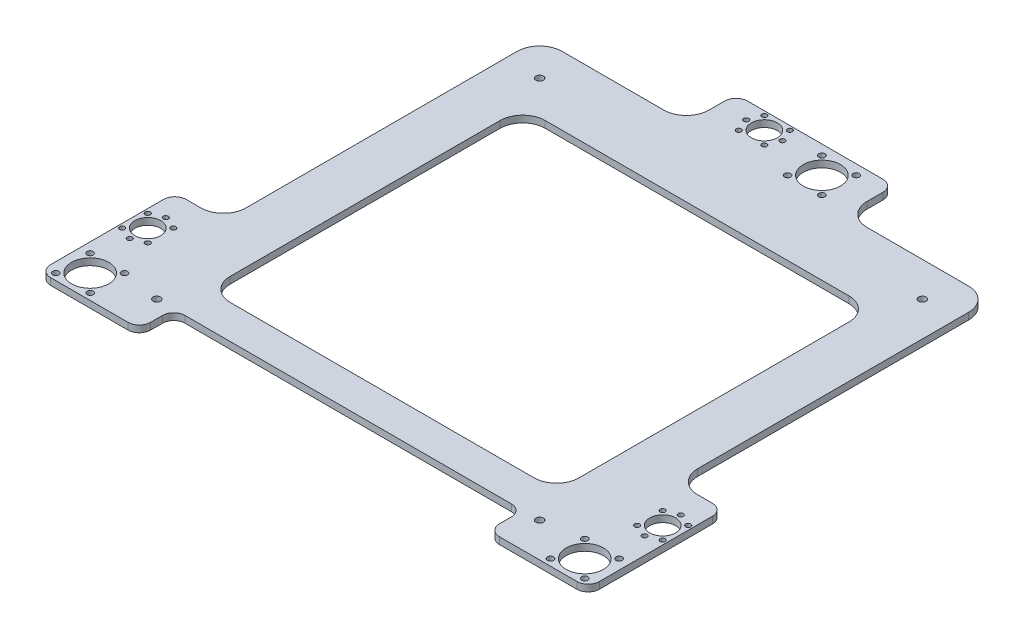
SolidWorks part; units mm, degrees
material "Plain Carbon Steel"
ref_plane "Front Plane" through (0, 0, 0) normal (0, 0, 1) x (1, 0, 0)
ref_plane "Top Plane" through (0, 0, 0) normal (0, 1, 0) x (1, 0, 0)
ref_plane "Right Plane" through (0, 0, 0) normal (1, 0, 0) x (0, 0, -1)
sketch "Sketch1" plane through (0, 0, 0) normal (0, 1, 0) x (1, 0, 0)
  line L0 (-243, -200) -> (243, -200)
  line L1 (-169.5, 169.5) -> (169.5, 169.5)
  line L2 (-169.5, 169.5) -> (-169.5, -169.5)
  line L3 (-169.5, -169.5) -> (169.5, -169.5)
  line L4 (169.5, 169.5) -> (169.5, -169.5)
  line L5 (-169.5, 169.5) -> (169.5, -169.5) construction
  line L6 (-169.5, -169.5) -> (169.5, 169.5) construction
  line L7 (-243, -200) -> (-243, 244)
  line L8 (-243, 244) -> (243, 244)
  line L9 (243, 244) -> (243, -200)
  line L10 (0, 0) -> (0, -200)
  point P0 (0, 0)
  point P12 (0, 0)
  point P13 (0, 0)
  point P14 (0, 0)
  point P15 (0, 0)
  dimension "D1" = 339
  dimension "D2" = 444
  dimension "D3" = 486
  dimension "D4" = 200
sketch "Sketch2" plane through (0, 0, 0) normal (0, 1, 0) x (1, 0, 0)
  line L0 (243, 244) -> (243, -200) construction
  line L1 (-243, 244) -> (243, 244) construction
  line L2 (-243, -200) -> (-243, 244) construction
  line L3 (-243, -200) -> (243, -200) construction
  line L4 (243, 244) -> (243, -200)
  line L5 (-243, 244) -> (243, 244)
  line L6 (-243, -200) -> (-243, 244)
  line L7 (-243, -200) -> (243, -200)
extrude "Boss-Extrude1" add sketch "Sketch2" along normal blind 6
sketch "Sketch3" plane through (0, 6, 0) normal (0, 1, 0) x (1, 0, 0)
  circle A0 centre (-234.2028, -194.2028) radius 2.75 construction
  circle A1 centre (-203.7972, -194.2028) radius 2.75 construction
  circle A2 centre (-203.7972, -163.7972) radius 2.75 construction
  circle A3 centre (-234.2028, -163.7972) radius 2.75 construction
  circle A4 centre (-234.2028, -194.2028) radius 2.75
  circle A5 centre (-203.7972, -194.2028) radius 2.75
  circle A6 centre (-203.7972, -163.7972) radius 2.75
  circle A7 centre (-234.2028, -163.7972) radius 2.75
  circle A8 centre (-239.3137, -130.3137) radius 2.35 construction
  circle A9 centre (-239.3137, -130.3137) radius 2.35 construction
  circle A10 centre (-239.3137, -107.6863) radius 2.35 construction
  circle A11 centre (-239.3137, -107.6863) radius 2.35 construction
  circle A12 centre (-228, -103) radius 2.35 construction
  circle A13 centre (-228, -103) radius 2.35 construction
  circle A14 centre (-216.6863, -107.6863) radius 2.35 construction
  circle A15 centre (-216.6863, -107.6863) radius 2.35 construction
  circle A16 centre (-216.6863, -130.3137) radius 2.35 construction
  circle A17 centre (-216.6863, -130.3137) radius 2.35 construction
  circle A18 centre (-228, -135) radius 2.35 construction
  circle A19 centre (-228, -135) radius 2.35 construction
  circle A20 centre (-239.3137, -130.3137) radius 2.35
  circle A21 centre (-239.3137, -130.3137) radius 2.35
  circle A22 centre (-239.3137, -107.6863) radius 2.35
  circle A23 centre (-239.3137, -107.6863) radius 2.35
  circle A24 centre (-228, -103) radius 2.35
  circle A25 centre (-228, -103) radius 2.35
  circle A26 centre (-216.6863, -107.6863) radius 2.35
  circle A27 centre (-216.6863, -107.6863) radius 2.35
  circle A28 centre (-216.6863, -130.3137) radius 2.35
  circle A29 centre (-216.6863, -130.3137) radius 2.35
  circle A30 centre (-228, -135) radius 2.35
  circle A31 centre (-228, -135) radius 2.35
  circle A32 centre (-228, -119) radius 11 construction
  circle A33 centre (-219, -179) radius 16 construction
  circle A34 centre (-228, -119) radius 11
  circle A35 centre (-219, -179) radius 16
  circle A36 centre (-41.3137, 240.3137) radius 2.35 construction
  circle A37 centre (-41.3137, 240.3137) radius 2.35 construction
  circle A38 centre (-18.6863, 240.3137) radius 2.35 construction
  circle A39 centre (-18.6863, 240.3137) radius 2.35 construction
  circle A40 centre (-14, 229) radius 2.35 construction
  circle A41 centre (-14, 229) radius 2.35 construction
  circle A42 centre (-18.6863, 217.6863) radius 2.35 construction
  circle A43 centre (-18.6863, 217.6863) radius 2.35 construction
  circle A44 centre (-41.3137, 217.6863) radius 2.35 construction
  circle A45 centre (-41.3137, 217.6863) radius 2.35 construction
  circle A46 centre (-46, 229) radius 2.35 construction
  circle A47 centre (-46, 229) radius 2.35 construction
  circle A48 centre (-41.3137, 240.3137) radius 2.35
  circle A49 centre (-41.3137, 240.3137) radius 2.35
  circle A50 centre (-18.6863, 240.3137) radius 2.35
  circle A51 centre (-18.6863, 240.3137) radius 2.35
  circle A52 centre (-14, 229) radius 2.35
  circle A53 centre (-14, 229) radius 2.35
  circle A54 centre (-18.6863, 217.6863) radius 2.35
  circle A55 centre (-18.6863, 217.6863) radius 2.35
  circle A56 centre (-41.3137, 217.6863) radius 2.35
  circle A57 centre (-41.3137, 217.6863) radius 2.35
  circle A58 centre (-46, 229) radius 2.35
  circle A59 centre (-46, 229) radius 2.35
  circle A60 centre (-30, 229) radius 11 construction
  circle A61 centre (30, 220) radius 16 construction
  circle A62 centre (14.7972, 235.2028) radius 2.75 construction
  circle A63 centre (45.2028, 235.2028) radius 2.75 construction
  circle A64 centre (45.2028, 204.7972) radius 2.75 construction
  circle A65 centre (14.7972, 204.7972) radius 2.75 construction
  circle A66 centre (-30, 229) radius 11
  circle A67 centre (30, 220) radius 16
  circle A68 centre (14.7972, 235.2028) radius 2.75
  circle A69 centre (45.2028, 235.2028) radius 2.75
  circle A70 centre (45.2028, 204.7972) radius 2.75
  circle A71 centre (14.7972, 204.7972) radius 2.75
hole_wizard "M5 Clearance Hole1" positions "Sketch4" profile "Sketch5" hole size "M5" standard "ANSI Metric" end condition through all
sketch "Sketch4" plane through (0, 6, 0) normal (0, 1, 0) x (1, 0, 0)
  point P0 (-203.7972, -163.7972)
  point P3 (-234.2028, -163.7972)
  point P6 (-234.2028, -194.2028)
  point P9 (-203.7972, -194.2028)
sketch "Sketch5" plane through (-203.7972, 6, 163.7972) normal (1, 0, 0) x (0, 0, 1)
  line L0 (0, 0) -> (0, 6)
  line L1 (0, 6) -> (2.75, 6)
  line L2 (2.75, 6) -> (2.75, 0)
  line L5 (2.75, 0) -> (0, 0)
  line L11 (0, -6.35) -> (0, 107.95) construction
  dimension "Thru Hole Dia." = 5.5
  dimension "Thru Hole Depth" = 6
hole_wizard "M4 Clearance Hole1" positions "Sketch6" profile "Sketch7" hole size "M4" standard "ANSI Metric" end condition through all
sketch "Sketch6" plane through (0, 6, 0) normal (0, 1, 0) x (1, 0, 0)
  point P0 (-228, -103)
  point P3 (-216.6863, -107.6863)
  point P6 (-216.6863, -130.3137)
  point P9 (-228, -135)
  point P12 (-239.3137, -130.3137)
  point P15 (-239.3137, -107.6863)
sketch "Sketch7" plane through (-228, 6, 103) normal (1, 0, 0) x (0, 0, 1)
  line L0 (0, 0) -> (0, 6)
  line L1 (0, 6) -> (2.25, 6)
  line L2 (2.25, 6) -> (2.25, 0)
  line L5 (2.25, 0) -> (0, 0)
  line L11 (0, -6.35) -> (0, 107.95) construction
  dimension "Thru Hole Dia." = 4.5
  dimension "Thru Hole Depth" = 6
sketch "Sketch8" plane through (0, 6, 0) normal (0, 1, 0) x (1, 0, 0)
  circle A0 centre (-228, -119) radius 11.5
  circle A1 centre (-219, -179) radius 16.5
  circle A2 centre (-219, -179) radius 16 construction
  circle A3 centre (-228, -119) radius 11 construction
  dimension "D1" = 0.5
  dimension "D2" = 0.5
extrude "Cut-Extrude1" cut sketch "Sketch8" against normal through all
mirror "Mirror1" about plane through (0, 0, 0) normal (1, 0, 0) of "Cut-Extrude1", "M4 Clearance Hole1", "M5 Clearance Hole1"
hole_wizard "M5 Clearance Hole2" positions "Sketch9" profile "Sketch10" hole size "M5" standard "ANSI Metric" end condition through all
sketch "Sketch9" plane through (0, 6, 0) normal (0, 1, 0) x (1, 0, 0)
  point P0 (14.7972, 204.7972)
  point P3 (45.2028, 204.7972)
  point P6 (45.2028, 235.2028)
  point P9 (14.7972, 235.2028)
sketch "Sketch10" plane through (14.7972, 6, -204.7972) normal (1, 0, 0) x (0, 0, 1)
  line L0 (0, 0) -> (0, 6)
  line L1 (0, 6) -> (2.75, 6)
  line L2 (2.75, 6) -> (2.75, 0)
  line L5 (2.75, 0) -> (0, 0)
  line L11 (0, -6.35) -> (0, 107.95) construction
  dimension "Thru Hole Dia." = 5.5
  dimension "Thru Hole Depth" = 6
hole_wizard "M4 Clearance Hole2" positions "Sketch11" profile "Sketch12" hole size "M4" standard "ANSI Metric" end condition through all
sketch "Sketch11" plane through (0, 6, 0) normal (0, 1, 0) x (1, 0, 0)
  point P0 (-18.6863, 217.6863)
  point P3 (-14, 229)
  point P6 (-18.6863, 240.3137)
  point P9 (-41.3137, 240.3137)
  point P12 (-46, 229)
  point P15 (-41.3137, 217.6863)
sketch "Sketch12" plane through (-18.6863, 6, -217.6863) normal (1, 0, 0) x (0, 0, 1)
  line L0 (0, 0) -> (0, 6)
  line L1 (0, 6) -> (2.25, 6)
  line L2 (2.25, 6) -> (2.25, 0)
  line L5 (2.25, 0) -> (0, 0)
  line L11 (0, -6.35) -> (0, 107.95) construction
  dimension "Thru Hole Dia." = 4.5
  dimension "Thru Hole Depth" = 6
sketch "Sketch13" plane through (0, 6, 0) normal (0, 1, 0) x (1, 0, 0)
  circle A0 centre (-30, 229) radius 11.5
  circle A1 centre (30, 220) radius 16.5
  circle A3 centre (-228, -119) radius 11.5 construction
  circle A4 centre (-219, -179) radius 16.5 construction
extrude "Cut-Extrude2" cut sketch "Sketch13" against normal through all
hole_wizard "M6 Clearance Hole1" positions "Sketch15" profile "Sketch16" hole size "M6" standard "ANSI Metric" end condition through all
sketch "Sketch15" plane through (0, 6, 0) normal (0, 1, 0) x (1, 0, 0)
  point P0 (-169.5, -169.5)
  point P2 (-169.5, 169.5)
  point P4 (169.5, 169.5)
  point P6 (169.5, -169.5)
  point P10 (0, 0)
  point P11 (0, 0)
  point P14 (0, 0)
  point P15 (0, 0)
sketch "Sketch16" plane through (-169.5, 6, 169.5) normal (1, 0, 0) x (0, 0, 1)
  line L0 (0, 0) -> (0, 6)
  line L1 (0, 6) -> (3.3, 6)
  line L2 (3.3, 6) -> (3.3, 0)
  line L5 (3.3, 0) -> (0, 0)
  line L11 (0, -6.35) -> (0, 107.95) construction
  dimension "Thru Hole Dia." = 6.6
  dimension "Thru Hole Depth" = 6
sketch "Sketch17" plane through (0, 6, 0) normal (0, 1, 0) x (1, 0, 0)
  line L1 (154.5, 139.5) -> (-154.5, 139.5)
  line L2 (154.5, 139.5) -> (154.5, -139.5)
  line L3 (154.5, -139.5) -> (-154.5, -139.5)
  line L4 (-154.5, 139.5) -> (-154.5, -139.5)
  line L5 (154.5, 139.5) -> (-154.5, -139.5) construction
  line L6 (154.5, -139.5) -> (-154.5, 139.5) construction
  point P0 (0, 0)
  dimension "D1" = 15
  dimension "D2" = 30
extrude "Cut-Extrude3" cut sketch "Sketch17" against normal through all
sketch "Sketch18" plane through (0, 6, 0) normal (0, 1, 0) x (1, 0, 0)
  line L0 (-243, -200) -> (243, -200) construction
  line L1 (-154.5, -200) -> (154.5, -200)
  line L2 (-154.5, -200) -> (-154.5, -169.5)
  line L3 (-154.5, -169.5) -> (154.5, -169.5)
  line L4 (154.5, -200) -> (154.5, -169.5)
  line L5 (-169.5, -169.5) -> (169.5, -169.5) construction
  line L6 (0, -169.5) -> (0, 0) construction
  point P6 (27.7033, -169.5)
  dimension "D1" = 15
extrude "Cut-Extrude4" cut sketch "Sketch18" against normal through all
sketch "Sketch19" plane through (0, 6, 0) normal (0, 1, 0) x (1, 0, 0)
  line L0 (-243, -80) -> (-200, -80)
  line L1 (-243, 244) -> (-243, -200) construction
  line L2 (-200, -80) -> (-200, 200)
  line L3 (-200, 200) -> (-70, 200)
  line L4 (-70, 200) -> (-70, 244)
  line L5 (243, 244) -> (-243, 244) construction
  line L6 (0, 0) -> (0, -200) construction
  line L7 (-243, -200) -> (243, -200) construction
  line L8 (-243, -80) -> (-243, 244)
  line L9 (-243, 244) -> (-70, 244)
  dimension "D1" = 200
  dimension "D2" = 200
  dimension "D3" = 70
  dimension "D4" = 120
extrude "Cut-Extrude5" cut sketch "Sketch19" against normal through all
mirror "Mirror2" about plane through (0, 0, 0) normal (1, 0, 0) of "Cut-Extrude5"
fillet "Fillet1" radius 10 10 edges at (-70, 3, -244) (70, 3, -244) (243, 3, 80) (243, 3, 200) (-243, 3, 80) (-243, 3, 200) (-154.5, 3, 200) (-154.5, 3, 169.5) (154.5, 3, 200) (154.5, 3, 169.5)
fillet "Fillet2" radius 20 10 edges at (200, 3, -200) (-200, 3, -200) (-154.5, 3, 139.5) (154.5, 3, 139.5) (154.5, 3, -139.5) (-154.5, 3, -139.5) (-200, 3, 80) (-70, 3, -200) (70, 3, -200) (200, 3, 80)
